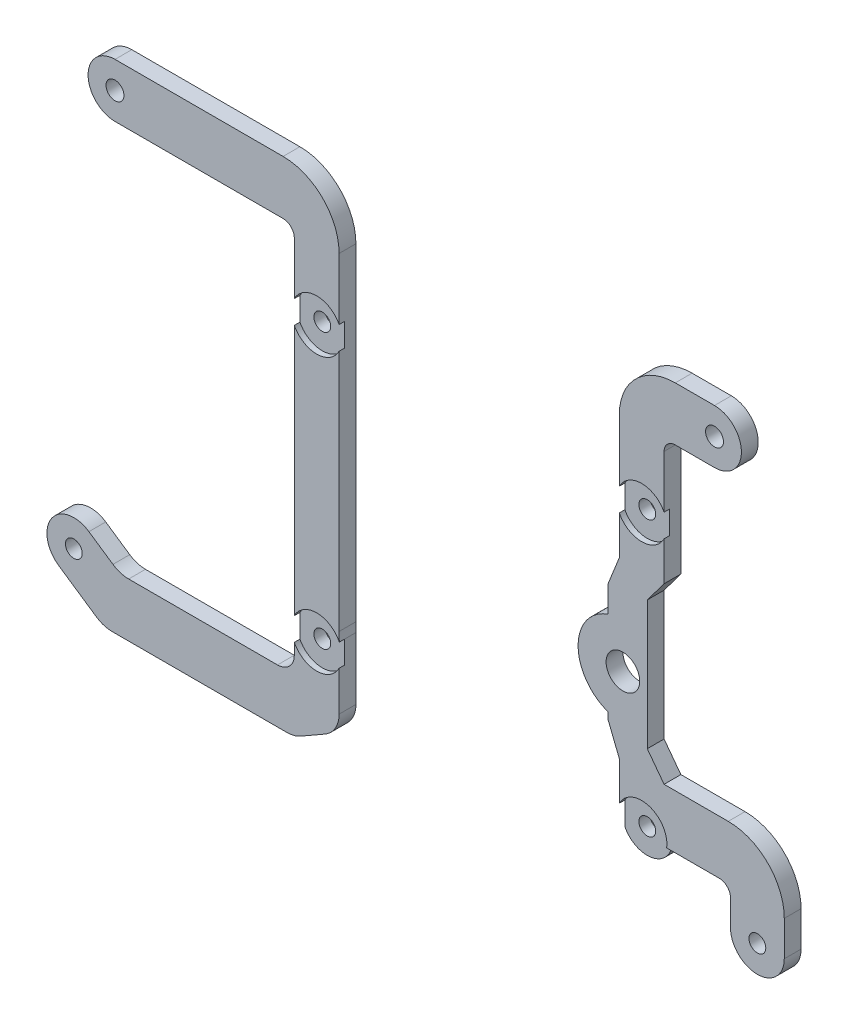
SolidWorks part; units mm, degrees
ref_plane "Front Plane" through (0, 0, 0) normal (0, 0, 1) x (1, 0, 0)
ref_plane "Top Plane" through (0, 0, 0) normal (0, 1, 0) x (1, 0, 0)
ref_plane "Right Plane" through (0, 0, 0) normal (1, 0, 0) x (0, 0, -1)
sketch "Sketch1" plane through (0, 0, 0) normal (0, 0, 1) x (1, 0, 0)
  line L0 (42, 25) -> (42, 16)
  line L1 (42, 16) -> (39, 12)
  line L2 (39, 12) -> (39, -11)
  line L3 (39, -11) -> (42, -15)
  line L4 (42, -15) -> (42, -24)
  line L5 (34, 25) -> (34, 16)
  line L6 (34, 16) -> (32, 11)
  line L7 (32, 11) -> (32, -10)
  line L8 (32, -10) -> (34, -15)
  line L9 (34, -15) -> (34, -24)
  line L10 (42, 16) -> (34, 16) construction
  line L11 (42, -15) -> (34, -15) construction
  line L12 (39, 12) -> (32, 11) construction
  line L13 (39, -11) -> (32, -10) construction
  line L14 (32, 0.5) -> (39, 0.5) construction
  circle A0 centre (38, 25) radius 4
  circle A1 centre (38, -24) radius 4
  circle A2 centre (38, -24) radius 1.5
  circle A3 centre (38, 25) radius 1.5
  dimension "D1" = 8
  dimension "D7" = 3
  dimension "D2" = 9
  dimension "D3" = 3
  dimension "D4" = 2
  dimension "D5" = 4
  dimension "D6" = 5
extrude "Boss-Extrude1" add sketch "Sketch1" along normal blind 3 contours A1 L4 L3 L2 L1 L0 A0 L5 L6 L7 L8 L9 | A0 A3 | A1 A2 region at (38, 21.1131, 0) region at (36.5126, 0.5, 0) region at (38, -27.8869, 0)
sketch "Sketch3" plane through (0, 0, 0) normal (0, 0, -1) x (-1, 0, 0)
  line L0 (20, 25) -> (20, -24) construction
  line L2 (16, -47.6521) -> (24, -47.6521)
  line L3 (16, -47.6521) -> (16, 48.6521)
  line L4 (16, 48.6521) -> (24, 48.6521)
  line L5 (24, -47.6521) -> (24, 48.6521)
  line L6 (16, -47.6521) -> (24, 48.6521) construction
  line L7 (16, 48.6521) -> (24, -47.6521) construction
  circle A0 centre (20, 25) radius 4
  circle A1 centre (20, -24) radius 4
  circle A2 centre (20, 25) radius 1.5
  circle A3 centre (20, -24) radius 1.5
  circle A4 centre (-38, 25) radius 1.5 construction
  point P10 (20, 0.5)
  dimension "D1" = 8
extrude "Boss-Extrude2" add sketch "Sketch3" against normal up to surface (3 mm away) separate body contours A0 L5 L4 L3 | A1 L5 A0 L3 | A0 A2 | A1 A3 | A1 L3 L2 L5 region at (-20, -37.3774, 0) region at (-20, 0.5, 0) region at (-20, -20.1131, 0) region at (-20, 38.3774, 0) region at (-20, 28.8869, 0) up to face at (37.1667, 0.5, 3)
sketch "Sketch4" plane through (0, 0, 3) normal (0, 0, 1) x (1, 0, 0)
  line L0 (38.3895, 40.9911) -> (42, 25)
  line L1 (29.7073, 38.65) -> (34, 25)
  line L2 (38, 25) -> (38, 15.9142) construction
  circle A0 centre (34, 40) radius 4.5
  circle A1 centre (34, 40) radius 1.5
  arc A2 (42, 25) -> (34, 25) centre (38, 25) ccw construction
  arc A3 (42, 25) -> (34, 25) centre (38, 25) ccw
  arc M8 (42, 25) -> (34, 25) centre (38, 25) ccw
  dimension "D1" = 9
  dimension "D2" = 3
  dimension "D3" = 15
  dimension "D4" = 4
extrude "Boss-Extrude3" add sketch "Sketch4" against normal up to surface (3 mm away) contours A0 L1 L0 M8 | A0 A1 region at (36.0637, 32.3875, 3) region at (38.3458, 40.4845, 3) up to face at (37.1667, 0.5, 0)
sketch "Sketch6" plane through (0, 0, 3) normal (0, 0, 1) x (1, 0, 0)
  line L0 (34, -24) -> (29.0588, -54.2751)
  line L1 (42, -24) -> (37.9637, -55.5707)
  circle A0 centre (33.5, -55) radius 1.5 construction
  circle A1 centre (33.5, -55) radius 1.5
  circle A2 centre (33.5, -55) radius 4.5
  arc A3 (34, -24) -> (42, -24) centre (38, -24) ccw construction
  arc A4 (34, -24) -> (42, -24) centre (38, -24) ccw
  arc M2 (34, -24) -> (42, -24) centre (38, -24) ccw
  dimension "D1" = 9
extrude "Boss-Extrude4" add sketch "Sketch6" against normal up to surface (3 mm away) contours A2 L1 L0 M2 | A2 A1 region at (35.7547, -39.5094, 3) region at (33.8533, -50.6416, 3) up to face at (36.9723, 7.527, 0)
sketch "Sketch7" plane through (0, 0, 3) normal (0, 0, 1) x (1, 0, 0)
  circle A0 centre (38, -24) radius 4.5
  circle A1 centre (38, 25) radius 4.5
  dimension "D1" = 9
extrude "Cut-Extrude1" cut sketch "Sketch7" against normal blind 1
sketch "Sketch8" plane through (0, 0, 0) normal (0, 0, 1) x (1, 0, 0)
  line L0 (33.7559, -25.4958) -> (29.0588, -54.2751) construction
  line L1 (34.0208, -51.8091) -> (30.997, -52.9535)
  line L2 (30.997, -52.9535) -> (30.4762, -56.1444)
  line L3 (30.4762, -56.1444) -> (32.9792, -58.1909)
  line L4 (32.9792, -58.1909) -> (36.003, -57.0465)
  line L5 (36.003, -57.0465) -> (36.5238, -53.8556)
  line L6 (36.5238, -53.8556) -> (34.0208, -51.8091)
  line L8 (38.3895, 40.9911) -> (41.3122, 28.0462) construction
  line L9 (34.7121, 36.8462) -> (37.0873, 39.0398)
  line L10 (37.0873, 39.0398) -> (36.3752, 42.1936)
  line L11 (36.3752, 42.1936) -> (33.2879, 43.1538)
  line L12 (33.2879, 43.1538) -> (30.9127, 40.9602)
  line L13 (30.9127, 40.9602) -> (31.6248, 37.8064)
  line L14 (31.6248, 37.8064) -> (34.7121, 36.8462)
  arc A0 (29.0588, -54.2751) -> (37.9637, -55.5707) centre (33.5, -55) ccw construction
  circle A1 centre (33.5, -55) radius 4.5
  circle A2 centre (33.5, -55) radius 2.8 construction
  arc A3 (38.3895, 40.9911) -> (29.7073, 38.65) centre (34, 40) ccw construction
  circle A4 centre (34, 40) radius 4.5
  circle A5 centre (34, 40) radius 2.8 construction
  dimension "D1" = 5.6
extrude "Boss-Extrude5" add sketch "Sketch8" against normal blind 2
sketch "Sketch9" plane through (0, 0, 0) normal (0, 0, 1) x (1, 0, 0)
  line L8 (31.6248, 37.8064) -> (34.7121, 36.8462)
  line L9 (30.9127, 40.9602) -> (31.6248, 37.8064)
  line L10 (33.2879, 43.1538) -> (30.9127, 40.9602)
  line L11 (36.3752, 42.1936) -> (33.2879, 43.1538)
  line L18 (37.0873, 39.0398) -> (36.3752, 42.1936)
  line L19 (34.7121, 36.8462) -> (37.0873, 39.0398)
  line L20 (31.6248, 37.8064) -> (34.7121, 36.8462)
  line L21 (30.9127, 40.9602) -> (31.6248, 37.8064)
  line L22 (33.2879, 43.1538) -> (30.9127, 40.9602)
  line L23 (36.3752, 42.1936) -> (33.2879, 43.1538)
  line L30 (37.0873, 39.0398) -> (36.3752, 42.1936)
  line L31 (34.7121, 36.8462) -> (37.0873, 39.0398)
  line L32 (36.5238, -53.8556) -> (34.0208, -51.8091)
  line L33 (36.003, -57.0465) -> (36.5238, -53.8556)
  line L34 (32.9792, -58.1909) -> (36.003, -57.0465)
  line L35 (30.4762, -56.1444) -> (32.9792, -58.1909)
  line L36 (30.997, -52.9535) -> (30.4762, -56.1444)
  line L37 (34.0208, -51.8091) -> (30.997, -52.9535)
  line L38 (36.5238, -53.8556) -> (34.0208, -51.8091)
  line L39 (36.003, -57.0465) -> (36.5238, -53.8556)
  line L40 (32.9792, -58.1909) -> (36.003, -57.0465)
  line L41 (30.4762, -56.1444) -> (32.9792, -58.1909)
  line L42 (30.997, -52.9535) -> (30.4762, -56.1444)
  line L43 (34.0208, -51.8091) -> (30.997, -52.9535)
  dimension "D1" = 0
  dimension "D2" = 0
extrude "Cut-Extrude2" cut sketch "Sketch9" along normal blind 1
sketch "Sketch11" plane through (0, 0, 0) normal (0, 0, -1) x (-1, 0, 0)
  line L0 (16, -47.6521) -> (16, 48.6521) construction
  line L1 (24, -47.6521) -> (24, 48.6521) construction
  line L2 (16, -47.6521) -> (24, -47.6521) construction
  line L3 (24, -47.6521) -> (24, 48.6521)
  line L4 (16, -47.6521) -> (24, -47.6521)
  line L5 (16, 48.6521) -> (24, 48.6521) construction
  line L6 (16, 48.6521) -> (24, 48.6521)
  line L7 (16, -47.6521) -> (16, 48.6521)
  circle A0 centre (9.9853, 42.5147) radius 1.5 construction
  circle A1 centre (9.9853, 42.5147) radius 1.5
  circle A2 centre (2.5, -55) radius 1.5 construction
  circle A3 centre (2.5, -55) radius 1.5
  circle A4 centre (2.5, -55) radius 4.5
  circle A5 centre (9.9853, 42.5147) radius 4.5
  arc A6 (-0.085, -51.3166) -> (16, -20.3773) centre (-21.7981, -20.3773) ccw
  arc A7 (5.085, -58.6834) -> (24, -30) centre (-21.7981, -20.3773) ccw
  arc A8 (11.52, 46.7449) -> (24, 33.8324) centre (4.5434, 27.5147) cw
  arc A9 (8.4506, 38.2845) -> (16, 27.5147) centre (4.5434, 27.5147) cw
  line M1 (16, 48.6521) -> (16, -47.6521)
  line M2 (16, -47.6521) -> (24, -47.6521)
  line M3 (24, -47.6521) -> (24, 48.6521)
  line M4 (24, 48.6521) -> (16, 48.6521)
  dimension "D1" = 9
  dimension "D2" = 15
  dimension "D3" = 25
extrude "Boss-Extrude6" add sketch "Sketch11" against normal up to surface (3 mm away) contours A5 A9 L7 A8 | A5 A1 | A4 A7 L7 A6 M2 | A4 A3 region at (-11.1205, -44.9713, 0) region at (1.0792, -57.5119, 0) region at (-14.3424, 38.0834, 0) region at (-13.5659, 45.0247, 0) up to face at (-20, 0.5, 3)
extrude "Cut-Extrude3" cut sketch "Sketch11<3>" against normal blind 10 contours A7 L4 M3 | A8 M1 M3 M4 region at (-21.6257, -42.4147, 0) region at (-20.804, 44.0025, 0)
sketch "Sketch11<3>" plane through (0, 0, 0) normal (0, 0, -1) x (-1, 0, 0) same geometry as "Sketch11"
fillet "Fillet1" radius 15 2 edges at (-24, 33.8324, 1.5) (-24, -30, 1.5)
sketch "Sketch13" plane through (0, 0, 3) normal (0, 0, 1) x (1, 0, 0)
  circle A0 centre (-20, 25) radius 4.5
  circle A1 centre (-20, -24) radius 4.5
  arc A2 (34, 22.9384) -> (42, 22.9384) centre (38, 25) ccw construction
extrude "Cut-Extrude4" cut sketch "Sketch13" against normal up to surface (1 mm away) up to face at (39.5, 25, 2)
sketch "Sketch14" plane through (0, 0, 0) normal (0, 0, 1) x (1, 0, 0)
  circle A0 centre (-9.9853, 42.5147) radius 2.8
  circle A1 centre (-2.5, -55) radius 2.8
  dimension "D1" = 5.6
extrude "Cut-Extrude5" cut sketch "Sketch14" along normal blind 1
sketch "Sketch15" plane through (0, 0, 0) normal (0, 0, -1) x (-1, 0, 0)
  line L2 (64.85, 44.75) -> (54.85, 44.75)
  line L3 (54.85, 41.75) -> (64.85, 41.75)
  line L4 (64.85, 44.75) -> (54.85, 44.75)
  line L5 (54.85, 41.75) -> (64.85, 41.75)
  line L7 (-60.15, 41.75) -> (-50.15, 41.75)
  line L8 (-50.15, 44.75) -> (-60.15, 44.75)
  line L9 (-60.15, 41.75) -> (-50.15, 41.75)
  line L10 (-50.15, 44.75) -> (-60.15, 44.75)
  circle A0 centre (-46.65, -1.25) radius 1.5 construction
  circle A1 centre (-46.65, -1.25) radius 1.5
  arc A2 (54.85, 44.75) -> (54.85, 41.75) centre (54.85, 43.25) ccw
  arc A3 (64.85, 41.75) -> (64.85, 44.75) centre (64.85, 43.25) ccw
  arc A4 (54.85, 44.75) -> (54.85, 41.75) centre (54.85, 43.25) ccw
  arc A5 (64.85, 41.75) -> (64.85, 44.75) centre (64.85, 43.25) ccw
  arc A6 (-60.15, 44.75) -> (-60.15, 41.75) centre (-60.15, 43.25) ccw
  arc A7 (-50.15, 41.75) -> (-50.15, 44.75) centre (-50.15, 43.25) ccw
  arc A8 (-60.15, 44.75) -> (-60.15, 41.75) centre (-60.15, 43.25) ccw
  arc A9 (-50.15, 41.75) -> (-50.15, 44.75) centre (-50.15, 43.25) ccw
  circle A10 centre (-34.65, -1.25) radius 1.5 construction
  circle A11 centre (-34.65, -1.25) radius 1.5
  circle A12 centre (-22.65, -1.25) radius 1.5 construction
  circle A13 centre (-22.65, -1.25) radius 1.5
  circle A14 centre (-22.65, -31.25) radius 1.5 construction
  circle A15 centre (-22.65, -31.25) radius 1.5
  circle A16 centre (-34.65, -31.25) radius 1.5 construction
  circle A17 centre (-34.65, -31.25) radius 1.5
  circle A18 centre (-46.65, -31.25) radius 1.5 construction
  circle A19 centre (-46.65, -31.25) radius 1.5
  circle A20 centre (39.35, -1.25) radius 1.5 construction
  circle A21 centre (39.35, -1.25) radius 1.5
  circle A22 centre (63.35, -31.25) radius 1.5 construction
  circle A23 centre (63.35, -31.25) radius 1.5
  circle A24 centre (-58.65, -31.25) radius 1.5 construction
  circle A25 centre (-58.65, -31.25) radius 1.5
  dimension "D1" = 0
  dimension "D2" = 0
sketch "Sketch16" plane through (0, 0, 3) normal (0, 0, 1) x (1, 0, 0)
  line L0 (-24, 30.6633) -> (-24, 50.5683)
  line L1 (-24, 50.5683) -> (-1.7164, 50.5683)
  line L2 (-1.7164, 50.5683) -> (-1.7164, 28.393)
  line L3 (-1.7164, 28.393) -> (-16, 27.0616)
  line L4 (-16, 27.0616) -> (-16, 30.6633)
  line L5 (-16, 30.6633) -> (-24, 30.6633)
  line L6 (-24, -28.2891) -> (-24, -67.6144)
  line L7 (-24, -67.6144) -> (10.6179, -67.6144)
  line L8 (10.6179, -67.6144) -> (10.6179, -31.4176)
  line L9 (10.6179, -31.4176) -> (-16, -20.3773)
  line L10 (-16, -20.3773) -> (-16, -32.1356)
  line L11 (-16, -32.1356) -> (-24, -32.1356)
  line L12 (34, -21.9384) -> (34, -29.242)
  line L13 (34, -29.242) -> (42.4694, -29.242)
  line L14 (42.4694, -29.242) -> (42.4694, -67.6144)
  line L15 (42.4694, -67.6144) -> (23.4078, -67.6144)
  line L16 (23.4078, -67.6144) -> (23.4078, -41.1938)
  line L17 (23.4078, -41.1938) -> (34, -21.9384)
  line L18 (34, 25) -> (34, 30.6633)
  line L19 (34, 30.6633) -> (25.2374, 30.6633)
  line L20 (25.2374, 30.6633) -> (25.2374, 48.5784)
  line L21 (25.2374, 48.5784) -> (45.4354, 48.5784)
  line L22 (45.4354, 48.5784) -> (45.4354, 22.9384)
  line L23 (45.4354, 22.9384) -> (42, 22.9384)
  line L24 (42, 22.9384) -> (42, 30.6633)
  line L25 (42, 30.6633) -> (34, 30.6633)
  line L26 (25.2374, 30.6633) -> (25.2374, 22.9384)
  line L27 (25.2374, 22.9384) -> (34, 25)
  arc M9 (-24, -21.9384) -> (-15.9648, -22.0082) centre (-20, -24) cw
  arc M10 (-15.9648, -22.0082) -> (-16, -20.3773) centre (21.7981, -20.3773) cw
extrude "Cut-Extrude6" cut sketch "Sketch16" against normal blind 10 contours L5 L4 L3 L2 L1 L0 | L25 L24 L23 L22 L21 L20 L19 | L26 L27 L18 L19 | L17 L16 L15 L14 L13 L12 | L10 L11 L6 L7 L8 L9 M10 M9 region at (-12.5593, 39.6271, 3) region at (-6.6821, -47.2943, 3) region at (33.3408, -48.8245, 3) region at (29.3938, 27.2898, 3) region at (35.9091, 38.7448, 3)
sketch "Sketch17" plane through (0, 0, 2) normal (0, 0, 1) x (1, 0, 0)
  line L0 (63.45, -31.25) -> (63.45, -15)
  line L1 (63.45, -15) -> (42, -15)
  line L2 (53.85, -31.25) -> (53.85, -24.6)
  line L3 (53.85, -24.6) -> (42, -24.6)
  line L4 (42, -21.9384) -> (42, -24) construction
  line L5 (42, -15) -> (42, -21.9384) construction
  line L6 (42, -15) -> (42, -21.9384)
  line L7 (42, -21.9384) -> (42, -24.6)
  circle A0 centre (58.65, -31.25) radius 1.5 construction
  circle A1 centre (58.65, -31.25) radius 1.5
  circle A2 centre (58.65, -31.25) radius 2.8
  circle A4 centre (58.65, -31.25) radius 4.8
  point P11 (41.9677, -24.5073)
  line M11 (42, -24) -> (42, -21.9384)
  dimension "D1" = 5.6
  dimension "D2" = 2
  dimension "D3" = 9.6
  dimension "D4" = 9.6
extrude "Boss-Extrude7" add sketch "Sketch17" against normal up to surface (2 mm away) contours A4 L0 L1 L6 L7 L3 L2 M11 | A4 A2 | A2 A1 region at (53.4264, -20.5623, 2) region at (58.65, -35.9142, 2) region at (55.9292, -31.25, 2) up to face at (39.5, 25, 0)
sketch "Sketch18" plane through (0, 0, 3) normal (0, 0, 1) x (1, 0, 0)
  line L0 (42, -15) -> (42, -21.9384) construction
  line L1 (34, -26.0616) -> (32.0296, -30.819)
  line L2 (32.0296, -30.819) -> (38, -35.9718)
  line L3 (38, -35.9718) -> (45.7702, -27.7408)
  line L4 (45.7702, -27.7408) -> (42.4598, -24.6)
  line L5 (53.85, -24.6) -> (42, -24.6) construction
  line L6 (42, -21.9384) -> (40.3944, -24.9079)
  line L7 (40.3944, -24.9079) -> (41.0513, -27.3075)
  arc A0 (34, -26.0616) -> (41.6664, -26.6091) centre (38, -24) ccw construction
  arc A1 (34, -26.0616) -> (42, -21.9384) centre (38, -24) ccw
  arc M1 (41.6664, -26.6091) -> (34, -26.0616) centre (38, -24) cw
  line M2 (34, -26.0616) -> (34, -29.242)
  line M3 (34, -29.242) -> (41.3298, -29.242)
  line M4 (41.3298, -29.242) -> (41.6664, -26.6091)
extrude "Cut-Extrude7" cut sketch "Sketch18" against normal blind 10 contours M4 M1 M2 M3 | A1 L1 L2 L3 L4 M4 M3 M2 region at (38.7398, -30.6093, 3) region at (37.2026, -28.5131, 3)
sketch "Sketch19" plane through (0, 0, 2) normal (0, 0, 1) x (1, 0, 0)
  line L0 (41.8418, -21.6568) -> (40.4124, -27.7987)
  arc A0 (34, -26.0616) -> (41.6664, -26.6091) centre (38, -24) ccw construction
  arc A1 (34, -26.0616) -> (41.8418, -21.6568) centre (38, -24) ccw
  arc M3 (34, -26.0616) -> (41.6664, -26.6091) centre (38, -24) ccw
  line M4 (41.6664, -26.6091) -> (41.8713, -25.0064)
  arc M5 (41.8713, -25.0064) -> (42, -24) centre (38, -24) ccw
  line M6 (42, -24) -> (42, -24.6)
  line M7 (42, -24.6) -> (53.85, -24.6)
  arc M13 (42, -21.9384) -> (34, -21.9384) centre (38, -24) ccw
extrude "Boss-Extrude9" add sketch "Sketch19" against normal up to surface (2 mm away) contours A1 L0 M7 M13 M3 M4 M5 M6 | A1 M4 M7 M6 M5 region at (41.5752, -24.7696, 2) region at (42.0421, -25.3573, 2) up to face at (39.5, 25, 0)
sketch "Sketch20" plane through (0, 0, 2) normal (0, 0, 1) x (1, 0, 0)
  line L0 (63.45, -31.25) -> (63.45, -15) construction
  line L1 (63.45, -31.25) -> (63.45, -15)
  line L2 (53.85, -31.25) -> (53.85, -24.6) construction
  line L3 (53.85, -31.25) -> (53.85, -24.6)
  line L4 (53.85, -24.6) -> (42.4598, -24.6) construction
  line L5 (53.85, -24.6) -> (42.4598, -24.6)
  line L6 (63.45, -15) -> (42, -15) construction
  line L7 (63.45, -15) -> (42, -15)
  line L8 (42, -15) -> (42, -21.9384) construction
  line L9 (42, -15) -> (42, -21.9384)
  arc A1 (53.85, -31.25) -> (63.45, -31.25) centre (58.65, -31.25) ccw construction
  arc A2 (53.85, -31.25) -> (63.45, -31.25) centre (58.65, -31.25) ccw
  arc A3 (42, -21.9384) -> (34, -21.9384) centre (38, -24) ccw construction
  arc A4 (42, -21.9384) -> (34, -21.9384) centre (38, -24) ccw
  arc A5 (34, -26.0616) -> (42.4598, -24.6) centre (38, -24) ccw construction
  circle A6 centre (38, -24) radius 4.5
  circle A7 centre (58.65, -31.25) radius 1.5 construction
  circle A8 centre (58.65, -31.25) radius 1.5
  point P9 (42.4598, -24.4364)
  point P11 (42, -21.9384)
  point P12 (42, -21.9384)
  point P17 (42.4598, -24.6)
  line M3 (42, -15) -> (42, -21.9384)
  line M7 (42.4598, -24.6) -> (53.85, -24.6)
  line M8 (53.85, -24.6) -> (53.85, -31.25)
  arc M9 (53.85, -31.25) -> (63.45, -31.25) centre (58.65, -31.25) ccw
  line M10 (63.45, -31.25) -> (63.45, -15)
  line M11 (63.45, -15) -> (42, -15)
extrude "Boss-Extrude10" add sketch "Sketch20" along normal up to surface (1 mm away) contours A6 M7 M8 M9 M10 M11 M3 region at (54.6088, -22.8957, 2) up to face at (37.1667, 0.5, 3)
fillet "Fillet2" radius 2 2 edges at (42.4598, -24.6, 1) (53.85, -24.6, 1.5)
fillet "Fillet3" radius 10 1 edges at (63.45, -15, 1.5)
sketch "Sketch21" plane through (0, 0, 3) normal (0, 0, 1) x (1, 0, 0)
  circle A0 centre (34.65, -1.25) radius 1.5 construction
  circle A1 centre (34.65, -1.25) radius 1.5 construction
  circle A2 centre (34.65, -1.25) radius 3
  circle A3 centre (22.65, -1.25) radius 3
  circle A4 centre (46.65, -1.25) radius 3
  circle A5 centre (34.65, -31.25) radius 3
  circle A6 centre (34.65, -1.25) radius 8
  line M11 (39, -11) -> (39, 12)
  line M17 (32, 11) -> (32, -10)
  dimension "D1" = 6
  dimension "D2" = 5
extrude "Boss-Extrude11" add sketch "Sketch21" against normal up to surface (3 mm away) contours A6 M11 | A6 A2 M17 | A2 M17 region at (31.8593, -1.25, 3) region at (29.76, -1.25, 3) region at (40.4929, -1.25, 3) up to face at (43.5619, -5.6049, 0)
extrude "Cut-Extrude8" cut sketch "Sketch21<3>" against normal through all contours A2 M17 | A2 M17 region at (34.7171, -1.25, 3) region at (31.8593, -1.25, 3)
sketch "Sketch21<3>" plane through (0, 0, 3) normal (0, 0, 1) x (1, 0, 0) same geometry as "Sketch21"
sketch "Sketch22" plane through (0, 0, 3) normal (0, 0, 1) x (1, 0, 0)
  line L0 (42, 22.9384) -> (42, 30.6633)
  line L1 (42, 30.6633) -> (38.9485, 30.6633)
  line L2 (40.7213, 30.6633) -> (34, 30.6633) construction
  line L4 (42, 22.9384) -> (42, 20.8727)
  line L5 (42, 22.9384) -> (42, 16) construction
  line L6 (42, 20.8727) -> (40.7508, 20.4335)
  line L7 (40.7508, 20.4335) -> (38.9485, 30.6633)
extrude "Boss-Extrude13" add sketch "Sketch22" against normal up to surface (3 mm away) up to face at (37.65, -1.25, 0)
sketch "Sketch23" plane through (0, 0, 2) normal (0, 0, 1) x (1, 0, 0)
  arc A0 (34, 22.9384) -> (40.5941, 21.323) centre (38, 25) ccw construction
  circle A1 centre (38, 25) radius 4.5
  point P3 (34, 23.3316)
extrude "Cut-Extrude9" cut sketch "Sketch23" along normal blind 27
sketch "Sketch24" plane through (0, 0, 3) normal (0, 0, 1) x (1, 0, 0)
  line L0 (50.15, 43.25) -> (60.15, 43.25) construction
  line L1 (51, 48.05) -> (34, 48.05)
  line L2 (34, 48.05) -> (34, 30.6633)
  line L3 (34, 30.6633) -> (42, 30.6633)
  line L4 (42, 30.6633) -> (42, 38.45)
  line L5 (42, 38.45) -> (51, 38.45)
  circle A1 centre (51, 43.25) radius 1.6
  circle A2 centre (51, 43.25) radius 4.8
  line M4 (42, 30.6633) -> (34, 30.6633)
  dimension "D1" = 3.2
  dimension "D2" = 9.6
  dimension "D3" = 17
extrude "Boss-Extrude14" add sketch "Sketch24" against normal up to surface (3 mm away) contours A2 L1 L2 L4 L5 M4 | A1 A2 region at (39.7836, 40.3893, 3) region at (54.2981, 46.5481, 3) up to face at (42.29, -7.5845, 0)
sketch "Sketch25" plane through (0, 0, 3) normal (0, 0, 1) x (1, 0, 0)
  line L0 (39, 5.464) -> (39, -7.964)
  line L1 (39, -7.964) -> (43.8925, -7.026)
  line L2 (43.8925, -7.026) -> (43.8925, 5.464)
  line L3 (43.8925, 5.464) -> (39, 5.464)
extrude "Cut-Extrude10" cut sketch "Sketch25" against normal through all
fillet "Fillet4" radius 2 1 edges at (42, 38.45, 1.5)
fillet "Fillet5" radius 10 1 edges at (34, 48.05, 1.5)
sketch "Sketch26" plane through (0, 0, 3) normal (0, 0, 1) x (1, 0, 0)
  line L0 (-64.85, 43.25) -> (-54.85, 43.25) construction
  line L1 (-56, 48.05) -> (-16, 48.05)
  line L2 (-16, 48.05) -> (-16, 30.6633)
  line L3 (-16, 30.6633) -> (-24, 30.6633)
  line L4 (-24, 30.6633) -> (-24, 38.45)
  line L5 (-24, 38.45) -> (-56, 38.45)
  circle A0 centre (-56, 43.25) radius 1.6
  circle A1 centre (-56, 43.25) radius 4.8
  line M4 (-16, 30.6633) -> (-24, 30.6633)
  dimension "D1" = 3.2
  dimension "D2" = 9.6
  dimension "D3" = 40
extrude "Boss-Extrude15" add sketch "Sketch26" against normal up to surface (3 mm away) contours A1 L5 L4 L2 L1 M4 | A1 A0 region at (-31.9844, 41.9295, 3) region at (-52.7019, 46.5481, 3) up to face at (-21.5, -24, 0)
fillet "Fillet6" radius 2 1 edges at (-24, 38.45, 1.5)
fillet "Fillet7" radius 10 1 edges at (-16, 48.05, 1.5)
sketch "Sketch27" plane through (0, 0, 3) normal (0, 0, 1) x (1, 0, 0)
  line L0 (-24, -28.2891) -> (-24, -32.1356)
  line L1 (-24, -32.1356) -> (-21.7061, -32.1356)
  line L2 (-16, -32.1356) -> (-23.4987, -32.1356) construction
  line L3 (-21.7061, -32.1356) -> (-24, -28.2891)
extrude "Boss-Extrude16" add sketch "Sketch27" against normal up to surface (3 mm away) up to face at (-21.5, -24, 0)
sketch "Sketch28" plane through (0, 0, 3) normal (0, 0, 1) x (1, 0, 0)
  line L0 (-63.35, -36.05) -> (-16, -36.05)
  line L1 (-16, -36.05) -> (-16, -32.1356)
  line L2 (-16, -32.1356) -> (-24, -32.1356)
  line L3 (-24, -32.1356) -> (-24, -26.45)
  line L4 (-24, -32.1356) -> (-24, -26.0616) construction
  line L5 (-24, -26.45) -> (-63.35, -26.45)
  circle A0 centre (-63.35, -31.25) radius 1.5 construction
  circle A1 centre (-63.35, -31.25) radius 1.5
  circle A2 centre (-63.35, -31.25) radius 4.8
  line M2 (-24, -26.0616) -> (-24, -32.1356)
  line M3 (-24, -32.1356) -> (-16, -32.1356)
  dimension "D1" = 9.6
extrude "Boss-Extrude17" add sketch "Sketch28" against normal up to surface (3 mm away) contours A2 L0 L1 L5 M3 M2 | A2 A1 region at (-39.9749, -31.4887, 3) region at (-68.0142, -31.25, 3) up to face at (-26.7535, 11.0354, 0)
sketch "Sketch30" plane through (0, 0, 3) normal (0, 0, 1) x (1, 0, 0)
  line L0 (-66.045, -35.222) -> (-58.045, -40.65)
  line L1 (-58.045, -40.65) -> (-24, -40.65)
  line L2 (-24, -40.65) -> (-16, -36.05)
  line L3 (-24, -24.8826) -> (-24, -31.05)
  line L4 (-24, -26.0616) -> (-24, -21.9384) construction
  line L5 (-24, -31.05) -> (-55.0956, -31.05)
  line L6 (-60.655, -27.278) -> (-55.0956, -31.05)
  line L7 (-63.35, -36.05) -> (-16, -36.05) construction
  line L8 (-24, -24.8826) -> (-65.5223, -20.8654)
  line L9 (-65.5223, -20.8654) -> (-63.35, -26.45)
  arc A0 (-63.35, -26.45) -> (-63.35, -36.05) centre (-63.35, -31.25) ccw construction
  circle A1 centre (-63.35, -31.25) radius 4.8
  line M7 (-24, -26.45) -> (-63.35, -26.45)
  arc M8 (-63.35, -26.45) -> (-63.35, -36.05) centre (-63.35, -31.25) ccw
  line M9 (-63.35, -36.05) -> (-16, -36.05)
  dimension "D1" = 5
  dimension "D2" = 9.6
  dimension "D3" = 8
  dimension "D4" = 8
extrude "Cut-Extrude11" cut sketch "Sketch30" against normal blind 10 contours A1 L6 L5 L3 M7 region at (-41.3257, -28.6719, 3)
extrude "Boss-Extrude18" add sketch "Sketch30<3>" against normal up to surface (3 mm away) contours L1 L2 L0 M9 M8 region at (-40.7259, -38.2107, 3) up to face at (-21.5, -24, 0)
sketch "Sketch30<3>" plane through (0, 0, 3) normal (0, 0, 1) x (1, 0, 0) same geometry as "Sketch30"
fillet "Fillet10" radius 3 1 edges at (-24, -31.05, 1.5)
fillet "Fillet11" radius 5 4 edges at (-58.045, -40.65, 1.5) (-55.0956, -31.05, 1.5) (-24, -40.65, 1.5) (-16, -36.05, 1.5)
